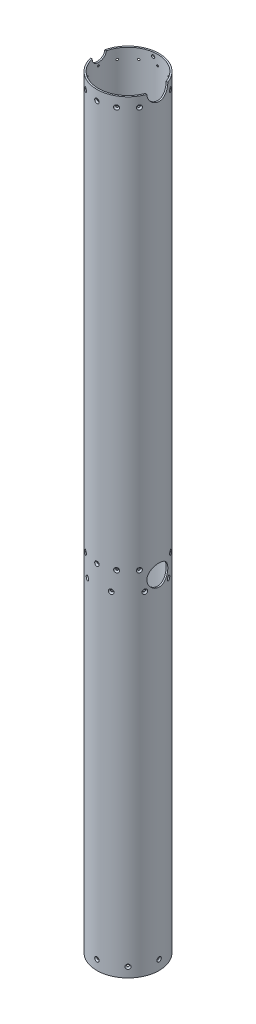
SolidWorks part; units mm, degrees
material "6063-T6"
ref_plane "Front Plane" through (0, 0, 0) normal (0, 0, 1) x (1, 0, 0)
ref_plane "Top Plane" through (0, 0, 0) normal (0, 1, 0) x (1, 0, 0)
ref_plane "Right Plane" through (0, 0, 0) normal (1, 0, 0) x (0, 0, -1)
sketch "Sketch1" plane through (0, 0, 0) normal (0, 1, 0) x (1, 0, 0)
  circle A0 centre (0, 0) radius 24.1554
  circle A1 centre (0, 0) radius 25.4
  dimension "D1" = 50.8
  dimension "D2" = 1.2446
extrude "body" add sketch "Sketch1" along normal blind 622.3
hole_wizard "M2x0.4 Tapped Hole1" positions "3DSketch1" profile "Sketch2" tap size "M2x0.4" standard "ANSI Metric"
sketch3d "3DSketch1"
  line L0 (25.4, 7.9375, 0) -> (-1.0246, 7.9375, 0)
  point P0 (25.4, 7.9375, 0)
sketch "Sketch2" plane through (25.4, 7.9375, 0) normal (0, 1, 0) x (0, 0, -1)
  line L0 (0, 0) -> (0, 8.3547)
  line L1 (0, 8.3547) -> (0.8, 7.874)
  line L2 (0.8, 7.874) -> (0.8, 1.09)
  line L3 (0.8, 1.09) -> (1.89, 0)
  line L4 (1.89, 0) -> (0, 0)
  line L5 (-0.8, 1.09) -> (-1.89, 0) construction
  line L6 (0, 8.3547) -> (-0.8, 7.874) construction
  line L7 (0, -6.35) -> (0, 107.95) construction
  dimension "Tap Drill Dia." = 1.6
  dimension "Tap Drill Depth" = 7.874
  dimension "Near C'Sink Dia." = 3.78
  dimension "Near C'Sink Angle" = 90
  dimension "Drill Angle" = 118
cosmetic thread "Hole Thread1" parameters "D1"=1.2579, "D2"=2
pattern_circular "CirPattern1" count 8 over 360 about axis through (0, 0, 0) along (0, 1, 0) of "M2x0.4 Tapped Hole1"
cosmetic thread "Hole Thread2" parameters "D1"=52.0579, "D2"=2
cosmetic thread "Hole Thread3" parameters "D1"=1.2579, "D2"=2
cosmetic thread "Hole Thread4" parameters "D1"=1.2579, "D2"=2
cosmetic thread "Hole Thread5" parameters "D1"=1.2579, "D2"=2
cosmetic thread "Hole Thread6" parameters "D1"=1.2579, "D2"=2
cosmetic thread "Hole Thread7" parameters "D1"=1.2579, "D2"=2
cosmetic thread "Hole Thread8" parameters "D1"=1.2579, "D2"=2
hole_wizard "M2x0.4 Tapped Hole2" positions "3DSketch2" profile "Sketch3" tap size "M2x0.4" standard "ANSI Metric"
sketch3d "3DSketch2"
  line L0 (23.4665, 271.4625, 9.7202) -> (2.1339, 271.4625, 0.8839)
  point P0 (23.4665, 271.4625, 9.7202)
sketch "Sketch3" plane through (23.4665, 271.4625, 9.7202) normal (0, 1, 0) x (0.3827, 0, -0.9239)
  line L0 (0, 0) -> (0, 8.3547)
  line L1 (0, 8.3547) -> (0.8, 7.874)
  line L2 (0.8, 7.874) -> (0.8, 1.09)
  line L3 (0.8, 1.09) -> (1.89, 0)
  line L4 (1.89, 0) -> (0, 0)
  line L5 (-0.8, 1.09) -> (-1.89, 0) construction
  line L6 (0, 8.3547) -> (-0.8, 7.874) construction
  line L7 (0, -6.35) -> (0, 107.95) construction
  dimension "Tap Drill Dia." = 1.6
  dimension "Tap Drill Depth" = 7.874
  dimension "Near C'Sink Dia." = 3.78
  dimension "Near C'Sink Angle" = 90
  dimension "Drill Angle" = 118
cosmetic thread "Hole Thread9" parameters "D1"=1.2579, "D2"=2
pattern_circular "CirPattern2" count 8 over 360 about axis through (0, 622.3, 0) along (0, -1, 0) of "M2x0.4 Tapped Hole2" reverse direction yes
cosmetic thread "Hole Thread10" parameters "D1"=1.2579, "D2"=2
cosmetic thread "Hole Thread11" parameters "D1"=1.2579, "D2"=2
cosmetic thread "Hole Thread12" parameters "D1"=1.2579, "D2"=2
cosmetic thread "Hole Thread13" parameters "D1"=1.2579, "D2"=2
cosmetic thread "Hole Thread14" parameters "D1"=52.0579, "D2"=2
cosmetic thread "Hole Thread15" parameters "D1"=1.2579, "D2"=2
cosmetic thread "Hole Thread16" parameters "D1"=1.2579, "D2"=2
hole_wizard "M2x0.4 Tapped Hole3" positions "3DSketch3" profile "Sketch4" tap size "M2x0.4" standard "ANSI Metric"
sketch3d "3DSketch3"
  line L0 (0, 614.172, 25.4) -> (0, 614.172, 15.3774)
  point P0 (0, 614.172, 25.4)
sketch "Sketch4" plane through (0, 614.172, 25.4) normal (1, 0, 0) x (0, -1, 0)
  line L0 (0, 0) -> (0, 8.3547)
  line L1 (0, 8.3547) -> (0.8, 7.874)
  line L2 (0.8, 7.874) -> (0.8, 1.09)
  line L3 (0.8, 1.09) -> (1.89, 0)
  line L4 (1.89, 0) -> (0, 0)
  line L5 (-0.8, 1.09) -> (-1.89, 0) construction
  line L6 (0, 8.3547) -> (-0.8, 7.874) construction
  line L7 (0, -6.35) -> (0, 107.95) construction
  dimension "Tap Drill Dia." = 1.6
  dimension "Tap Drill Depth" = 7.874
  dimension "Near C'Sink Dia." = 3.78
  dimension "Near C'Sink Angle" = 90
  dimension "Drill Angle" = 118
cosmetic thread "Hole Thread17" parameters "D1"=1.2579, "D2"=2
pattern_circular "CirPattern3" count 12 over 360 about axis through (0, 622.3, 0) along (0, -1, 0) skipping 9 of "M2x0.4 Tapped Hole3"
cosmetic thread "Hole Thread18" parameters "D1"=1.2579, "D2"=2
cosmetic thread "Hole Thread19" parameters "D1"=1.2579, "D2"=2
cosmetic thread "Hole Thread20" parameters "D1"=1.2579, "D2"=2
cosmetic thread "Hole Thread21" parameters "D1"=1.2579, "D2"=2
cosmetic thread "Hole Thread22" parameters "D1"=1.2579, "D2"=2
cosmetic thread "Hole Thread23" parameters "D1"=1.2579, "D2"=2
cosmetic thread "Hole Thread24" parameters "D1"=1.2579, "D2"=2
cosmetic thread "Hole Thread25" parameters "D1"=1.2579, "D2"=2
cosmetic thread "Hole Thread26" parameters "D1"=1.2579, "D2"=2
cosmetic thread "Hole Thread27" parameters "D1"=1.2579, "D2"=2
hole_wizard "M2x0.4 Tapped Hole4" positions "3DSketch4" profile "Sketch5" tap size "M2x0.4" standard "ANSI Metric"
sketch3d "3DSketch4"
  line L0 (-25.4, 287.3502, 0) -> (-18.8369, 287.3502, 0)
  point P0 (-25.4, 287.3502, 0)
sketch "Sketch5" plane through (-25.4, 287.3502, 0) normal (0, 1, 0) x (0, 0, 1)
  line L0 (0, 0) -> (0, 8.3547)
  line L1 (0, 8.3547) -> (0.8, 7.874)
  line L2 (0.8, 7.874) -> (0.8, 1.09)
  line L3 (0.8, 1.09) -> (1.89, 0)
  line L4 (1.89, 0) -> (0, 0)
  line L5 (-0.8, 1.09) -> (-1.89, 0) construction
  line L6 (0, 8.3547) -> (-0.8, 7.874) construction
  line L7 (0, -6.35) -> (0, 107.95) construction
  dimension "Tap Drill Dia." = 1.6
  dimension "Tap Drill Depth" = 7.874
  dimension "Near C'Sink Dia." = 3.78
  dimension "Near C'Sink Angle" = 90
  dimension "Drill Angle" = 118
cosmetic thread "Hole Thread28" parameters "D1"=1.2579, "D2"=2
pattern_circular "CirPattern4" count 12 over 360 about axis through (0, 622.3, 0) along (0, -1, 0) skipping 6 of "M2x0.4 Tapped Hole4" reverse direction yes
cosmetic thread "Hole Thread29" parameters "D1"=1.2579, "D2"=2
cosmetic thread "Hole Thread30" parameters "D1"=1.2579, "D2"=2
cosmetic thread "Hole Thread31" parameters "D1"=1.2579, "D2"=2
cosmetic thread "Hole Thread32" parameters "D1"=1.2579, "D2"=2
cosmetic thread "Hole Thread33" parameters "D1"=1.2579, "D2"=2
cosmetic thread "Hole Thread34" parameters "D1"=1.2579, "D2"=2
cosmetic thread "Hole Thread35" parameters "D1"=1.2579, "D2"=2
cosmetic thread "Hole Thread36" parameters "D1"=1.2579, "D2"=2
cosmetic thread "Hole Thread37" parameters "D1"=1.2579, "D2"=2
cosmetic thread "Hole Thread38" parameters "D1"=1.2579, "D2"=2
hole_wizard "43/64 (0.67188) Diameter Hole1" positions "3DSketch5" profile "Sketch6" hole size "43/64" standard "ANSI Inch"
sketch3d "3DSketch5"
  line L0 (25.4, 279.4, 0) -> (13.4323, 279.4, 0)
  point P0 (25.4, 279.4, 0)
  point P5 (25.4, 622.3, 0)
sketch "Sketch6" plane through (25.4, 279.4, 0) normal (0, 1, 0) x (0, 0, -1)
  line L0 (0, 0) -> (0, 33.8291)
  line L1 (0, 33.8291) -> (8.5329, 28.702)
  line L2 (8.5329, 28.702) -> (8.5329, 0)
  line L3 (8.5329, 0) -> (0, 0)
  line L4 (0, 33.8291) -> (-8.5329, 28.702) construction
  line L5 (0, -6.35) -> (0, 107.95) construction
  dimension "Hole Dia." = 17.0658
  dimension "Hole Depth" = 28.702
  dimension "Drill Angle" = 118
pattern_linear "LPattern1" [suppressed] of bodies 110
hole_wizard "7/16 Clearance Hole1" positions "3DSketch6" profile "Sketch7" hole size "7/16" standard "ANSI Inch"
sketch3d "3DSketch6"
  line L0 (-25.4, 279.4, 0) -> (-8.764, 279.4, 0)
  point P0 (-25.4, 279.4, 0)
  point P15 (-25.4, 622.3, 0)
sketch "Sketch7" plane through (-25.4, 279.4, 0) normal (0, 1, 0) x (0, 0, 1)
  line L0 (0, 0) -> (0, 32.1596)
  line L1 (0, 32.1596) -> (5.7544, 28.702)
  line L2 (5.7544, 28.702) -> (5.7544, 0)
  line L3 (5.7544, 0) -> (0, 0)
  line L4 (0, 32.1596) -> (-5.7544, 28.702) construction
  line L5 (0, -6.35) -> (0, 107.95) construction
  dimension "Hole Dia." = 11.5087
  dimension "Hole Depth" = 28.702
  dimension "Drill Angle" = 118
hole_wizard "3/32 (0.09375) Diameter Hole1" positions "Sketch8" profile "Sketch9" hole size "3/32" standard "ANSI Inch"
sketch "Sketch8" plane through (0, 0, -25.4) normal (0, 0, -1) x (-1, 0, 0)
  point P0 (3.4131, 619.125)
sketch "Sketch9" plane through (-3.4131, 619.125, -25.4) normal (1, 0, 0) x (0, 1, 0)
  line L0 (0, 0) -> (0, 30.6795)
  line L1 (0, 30.6795) -> (1.1906, 29.9641)
  line L2 (1.1906, 29.9641) -> (1.1906, 0)
  line L3 (1.1906, 0) -> (0, 0)
  line L4 (0, 30.6795) -> (-1.1906, 29.9641) construction
  line L5 (0, -6.35) -> (0, 107.95) construction
  dimension "Hole Dia." = 2.3812
  dimension "Hole Depth" = 29.9641
  dimension "Drill Angle" = 118
